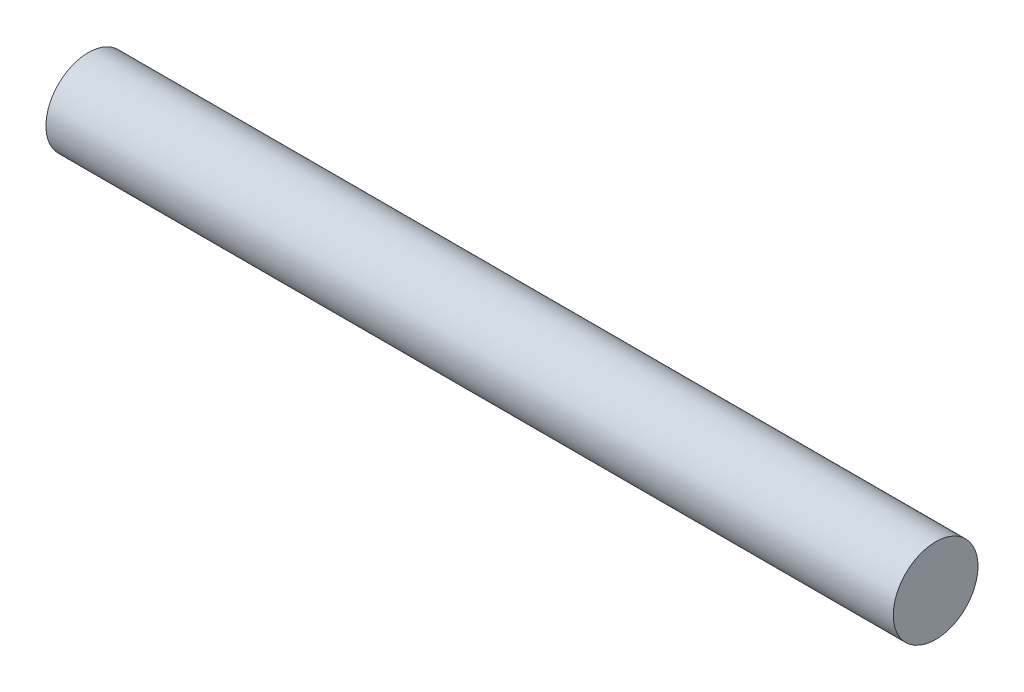
SolidWorks part; units mm, degrees
ref_plane "Front Plane" through (0, 0, 0) normal (0, 0, 1) x (1, 0, 0)
ref_plane "Top Plane" through (0, 0, 0) normal (0, 1, 0) x (1, 0, 0)
ref_plane "Right Plane" through (0, 0, 0) normal (1, 0, 0) x (0, 0, -1)
sketch "Sketch1" plane through (0, 0, 0) normal (1, 0, 0) x (0, 0, -1)
  circle A0 centre (0, 0) radius 0.635
  dimension "D1" = 1.27
extrude "Boss-Extrude1" add sketch "Sketch1" along normal blind 12.7
ref_axis "Axis1" through (12.7, 0, 0) along (-1, 0, 0)
